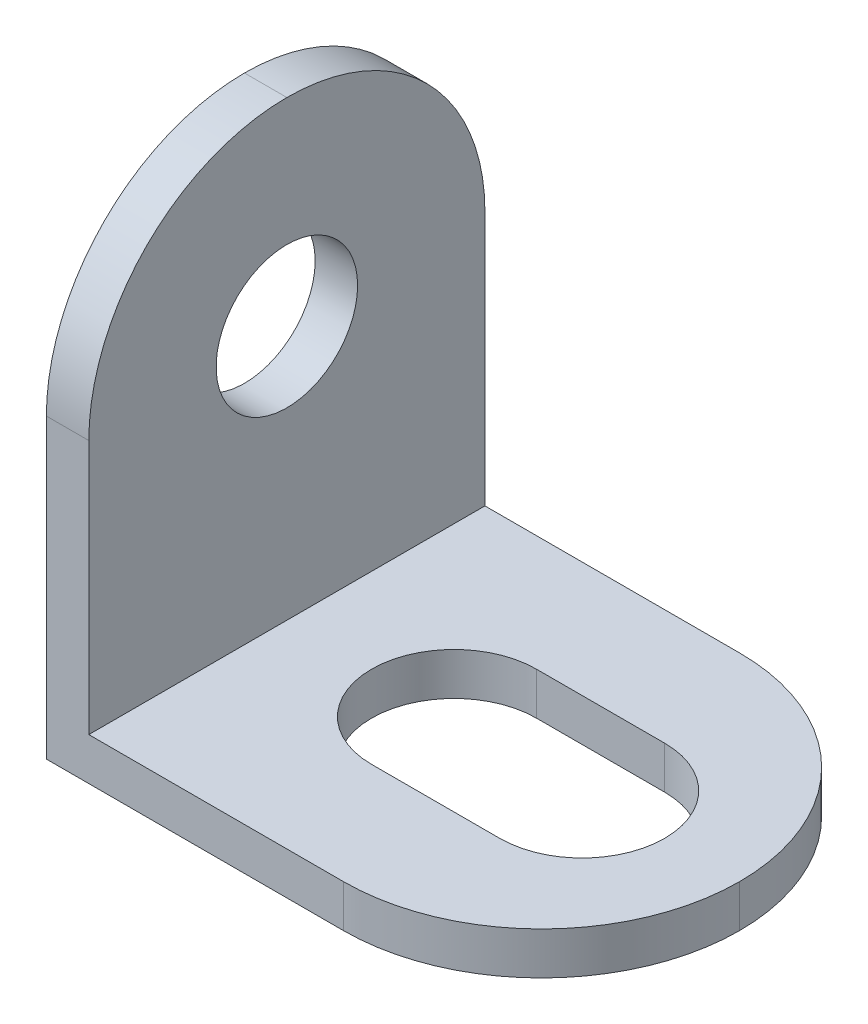
SolidWorks part; units mm, degrees
ref_plane "Front Plane" through (0, 0, 0) normal (0, 0, 1) x (1, 0, 0)
ref_plane "Top Plane" through (0, 0, 0) normal (0, 1, 0) x (1, 0, 0)
ref_plane "Right Plane" through (0, 0, 0) normal (1, 0, 0) x (0, 0, -1)
sketch "Sketch1" plane through (0, 0, 0) normal (0, 0, 1) x (1, 0, 0)
  line L0 (0, 0) -> (0, 16)
  line L1 (0, 0) -> (16, 0)
extrude "Extrude-Thin1" add sketch "Sketch1" along normal blind 14 thin thin type one direction wall 1.5
fillet "Fillet1" radius 7 4 edges at (16, -0.75, 14) (16, -0.75, 0) (-0.75, 16, 0) (-0.75, 16, 14)
sketch "Sketch2" plane through (0, 0, 0) normal (0, 1, 0) x (1, 0, 0)
  line L0 (16, -7) -> (25.3205, -7) construction
  line L1 (5.9069, -7) -> (10.4366, -7) construction
  line L2 (5.9069, -4.086) -> (10.4366, -4.086)
  line L3 (5.9069, -9.914) -> (10.4366, -9.914)
  arc A0 (5.9069, -4.086) -> (5.9069, -9.914) centre (5.9069, -7) ccw
  arc A1 (10.4366, -9.914) -> (10.4366, -4.086) centre (10.4366, -7) ccw
  point P3 (8.1718, -7)
extrude "Cut-Extrude1" cut sketch "Sketch2" against normal through all contours L2 A1 L3 A0
sketch "Sketch3" plane through (0, 0, 0) normal (1, 0, 0) x (0, 0, -1)
  circle A0 centre (-7, 9) radius 2.5
extrude "Cut-Extrude2" cut sketch "Sketch3" against normal through all
